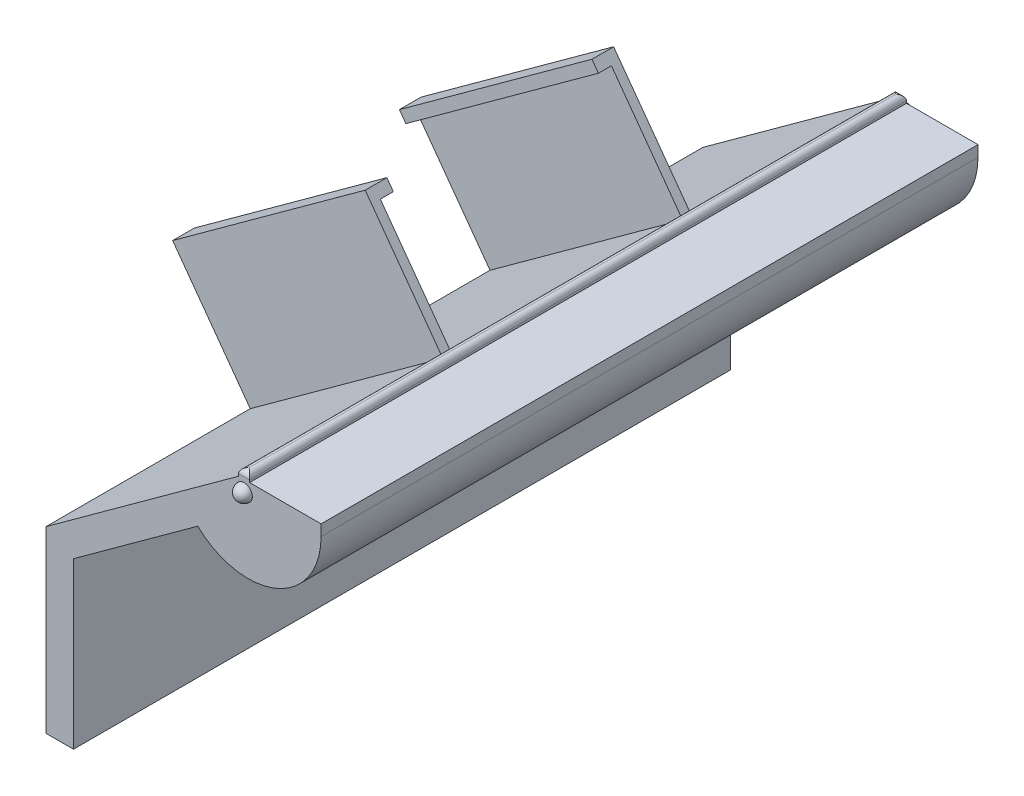
SolidWorks part; units mm, degrees
ref_plane "Front Plane" through (0, 0, 0) normal (0, 0, 1) x (1, 0, 0)
ref_plane "Top Plane" through (0, 0, 0) normal (0, 1, 0) x (1, 0, 0)
ref_plane "Right Plane" through (0, 0, 0) normal (1, 0, 0) x (0, 0, -1)
sketch "Sketch1" plane through (0, 0, 0) normal (0, 0, 1) x (1, 0, 0)
  line L0 (-38.1, -55.3082) -> (-9.4202, -34.4711)
  line L1 (2.54, -19.7779) -> (19.05, -19.7779)
  line L2 (-44.45, -52.0727) -> (-44.45, -93.4082)
  line L3 (-44.45, -93.4082) -> (-38.1, -93.4082)
  line L4 (-38.1, -55.3082) -> (-38.1, -93.4082)
  line L5 (-44.45, -52.0727) -> (0, -19.7779)
  line L6 (19.05, -19.7779) -> (19.05, -22.3179)
  line L7 (0, -38.9998) -> (0, -150.6026) construction
  line L9 (0, 29.1888) -> (0, -19.7779) construction
  line L10 (0, -19.7779) -> (0, -17.9999)
  line L11 (0, -17.9999) -> (2.54, -17.9999)
  line L12 (2.54, -17.9999) -> (2.54, -19.7779)
  arc A0 (-9.4202, -34.4711) -> (19.05, -22.3179) centre (2.221, -22.3179) ccw
  dimension "D1" = 6.35
  dimension "D2" = 6.35
  dimension "D3" = 2.54
  dimension "D4" = 126
  dimension "D5" = 38.1
  dimension "D6" = 38.1
  dimension "D7" = 19.05
  dimension "D8" = 2.54
  dimension "D9" = 1.778
extrude "Boss-Extrude1" add sketch "Sketch1" along normal mid plane 151.638
sketch "Sketch2" plane through (0, 0, 75.819) normal (0, 0, 1) x (1, 0, 0)
  line L0 (2.54, -17.9999) -> (0, -17.9999) construction
  line L2 (1.27, -20.4129) -> (1.27, -24.2229)
  arc A0 (1.27, -24.2229) -> (1.27, -20.4129) centre (1.27, -22.3179) ccw
  point P4 (1.27, -17.9999)
  dimension "D1" = 3.81
revolve "Revolve1" add sketch "Sketch2" angle 360 about L2
sketch "Sketch3" plane through (0, 0, -75.819) normal (0, 0, -1) x (-1, 0, 0)
  line L0 (-1.27, -20.4129) -> (-1.27, -24.2229)
  arc A0 (-1.27, -24.2229) -> (-1.27, -20.4129) centre (-1.27, -22.3179) ccw
  circle A1 centre (-1.27, -22.3179) radius 1.905 construction
revolve "Revolve2" add sketch "Sketch3" angle 360 about L0
fillet "Fillet2" radius 1.27 4 edges at (2.54, -17.9999, 0) (1.27, -17.9999, 75.819) (0, -17.9999, 0) (1.27, -17.9999, -75.819)
sketch "Sketch6" plane through (9.405, -12.9448, 0) normal (-0.5878, 0.809, 0) x (0.809, 0.5878, 0)
  line L0 (31.5068, 0) -> (-140.7073, 0) construction
  line L1 (-11.6252, 28.67) -> (-66.5684, 28.67)
  line L2 (-11.6252, 28.67) -> (-11.6252, 26.67)
  line L3 (-11.6252, 26.67) -> (-66.5684, 26.67)
  line L4 (-66.5684, 28.67) -> (-66.5684, 26.67)
  line L5 (-11.6252, -26.67) -> (-66.5684, -26.67)
  line L6 (-11.6252, -26.67) -> (-11.6252, -28.67)
  line L7 (-11.6252, -28.67) -> (-66.5684, -28.67)
  line L8 (-66.5684, -26.67) -> (-66.5684, -28.67)
  line L9 (-66.5684, -75.819) -> (-66.5684, 75.819) construction
  line L10 (-11.6252, -75.819) -> (-11.6252, 75.819) construction
  dimension "D1" = 26.67
  dimension "D2" = 26.67
  dimension "D3" = 2
extrude "Boss-Extrude4" add sketch "Sketch6" along normal blind 27.94
sketch "Sketch7" plane through (-7.0178, 9.6591, 0) normal (-0.5878, 0.809, 0) x (0.809, 0.5878, 0)
  line L0 (-66.5684, 23.67) -> (-11.6252, 23.67)
  line L1 (-11.6252, 28.67) -> (-66.5684, 28.67)
  line L2 (-11.6252, 28.67) -> (-11.6252, 23.67)
  line L3 (-11.6252, -28.67) -> (-66.5684, -28.67)
  line L4 (-66.5684, 28.67) -> (-66.5684, 23.67)
  line L5 (-66.5684, -23.67) -> (-11.6252, -23.67)
  line L6 (-66.5684, -23.67) -> (-66.5684, -28.67)
  line L7 (-11.6252, -23.67) -> (-11.6252, -28.67)
  dimension "D1" = 5
extrude "Boss-Extrude5" add sketch "Sketch7" along normal blind 2.54
